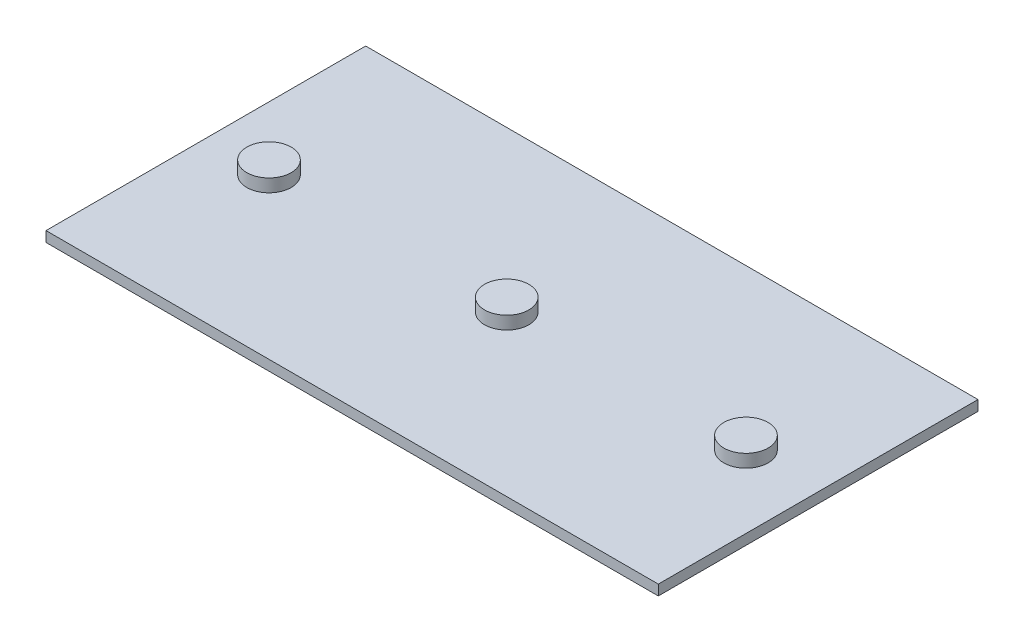
SolidWorks part; units mm, degrees
material "AISI 1020"
ref_plane "Plan de face" through (0, 0, 0) normal (0, 0, 1) x (1, 0, 0)
ref_plane "Plan de dessus" through (0, 0, 0) normal (0, 1, 0) x (1, 0, 0)
ref_plane "Plan de droite" through (0, 0, 0) normal (1, 0, 0) x (0, 0, -1)
sketch "Esquisse1" plane through (0, 0, 0) normal (0, 1, 0) x (1, 0, 0)
  line L1 (0, 0) -> (118.75, 0)
  line L2 (0, 0) -> (0, -62)
  line L3 (0, -62) -> (118.75, -62)
  line L4 (118.75, 0) -> (118.75, -62)
  point P4 (0, 0)
  dimension "D1" = 118.75
  dimension "D2" = 62
extrude "Boss.-Extru.1" add sketch "Esquisse1" along normal blind 2
sketch "Esquisse2" plane through (0, 0, 0) normal (0, -1, 0) x (1, 0, 0)
  line L0 (3.3, 0) -> (-3.3, 0) construction
  line L1 (95.75, 38.6) -> (110.75, 38.6)
  line L2 (95.75, 38.6) -> (95.75, 23)
  line L3 (95.75, 23) -> (110.75, 23)
  line L4 (110.75, 38.6) -> (110.75, 23)
  line L5 (118.75, 62) -> (118.75, 0) construction
  dimension "D1" = 15.6
  dimension "D2" = 23
  dimension "D3" = 8
  dimension "D4" = 15
extrude "Boss.-Extru.2" add sketch "Esquisse2" along normal blind 4
sketch "Esquisse3" plane through (0, 2, 0) normal (0, 1, 0) x (1, 0, 0)
  line L0 (19.2215, -31) -> (110.6537, -31) construction
  line L3 (118.75, 0) -> (118.75, -62) construction
  line L4 (0, -62) -> (118.75, -62) construction
  line L7 (-3.3, 0) -> (3.3, 0) construction
  line L8 (118.75, -62) -> (118.75, 0) construction
  circle A0 centre (104.75, -31) radius 4.3
  circle A1 centre (58.35, -31) radius 4.3
  circle A2 centre (12.25, -31) radius 4.3
  point P15 (118.75, -31)
  dimension "D1" = 8.6
  dimension "D2" = 46.4
  dimension "D3" = 14
  dimension "D4" = 46.1
extrude "Boss.-Extru.3" add sketch "Esquisse3" along normal blind 2.5
